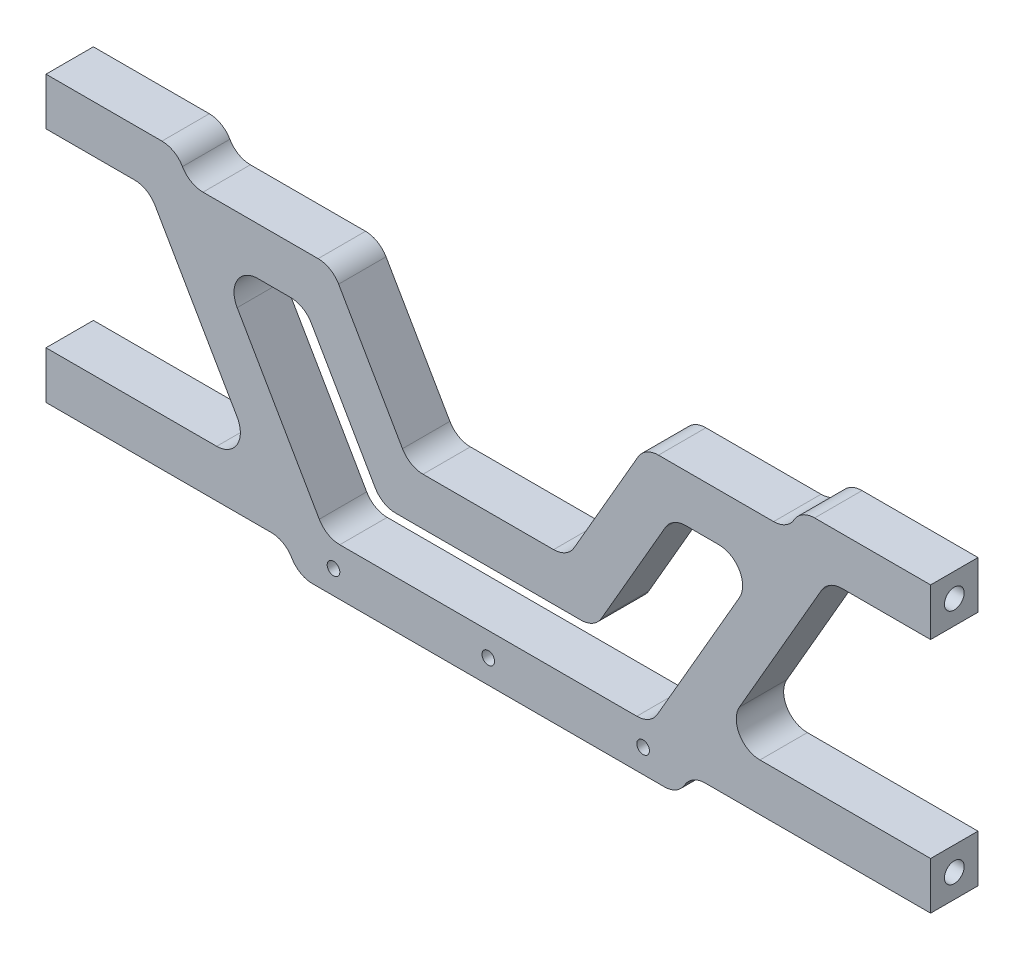
SolidWorks part; units mm, degrees
ref_plane "Front Plane" through (0, 0, 0) normal (0, 0, 1) x (1, 0, 0)
ref_plane "Top Plane" through (0, 0, 0) normal (0, 1, 0) x (1, 0, 0)
ref_plane "Right Plane" through (0, 0, 0) normal (1, 0, 0) x (0, 0, -1)
sketch "Sketch1" plane through (0, 0, 0) normal (0, 0, 1) x (1, 0, 0)
  line L1 (-56, 0) -> (56, 0)
  line L2 (-56, 0) -> (-56, 39)
  line L3 (-56, 39) -> (56, 39)
  line L4 (56, 0) -> (56, 39)
  dimension "D1" = 39
  dimension "D2" = 112
extrude "Boss-Extrude1" add sketch "Sketch1" along normal blind 6
sketch "Sketch2" plane through (0, 0, 6) normal (0, 0, 1) x (1, 0, 0)
  line L0 (-56, 33) -> (-43.0526, 33)
  line L2 (-56, 39) -> (-56, 0) construction
  line L3 (-43.0526, 33) -> (-29.1962, 9)
  line L5 (-29.1962, 9) -> (-56, 9)
  line L6 (-56, 9) -> (-56, 33)
  line L7 (56, 39) -> (-56, 39) construction
  line L8 (-39.5885, 39) -> (-37.8564, 36)
  line L9 (-10, 19) -> (0, 19)
  line L10 (0, 19) -> (0, 39)
  line L11 (0, 39) -> (-39.5885, 39)
  line L12 (-56, 3) -> (-25.7321, 3)
  line L13 (-25.7321, 3) -> (-24, 0)
  line L14 (-56, 0) -> (56, 0) construction
  line L15 (-24, 0) -> (-56, 0)
  line L16 (-56, 0) -> (-56, 3)
  line L17 (-13.4641, 13) -> (0, 13)
  line L18 (0, 13) -> (0, 6)
  line L19 (0, 6) -> (-20.5359, 6)
  line L20 (-20.5359, 6) -> (-34.3923, 30)
  line L21 (-37.8564, 36) -> (-19.815, 36)
  line L22 (-19.815, 36) -> (-10, 19)
  line L23 (-13.4641, 13) -> (-23.2791, 30)
  line L24 (-23.2791, 30) -> (-34.3923, 30)
  dimension "D3" = 60
  dimension "D1" = 6
  dimension "D2" = 24
  dimension "D4" = 6
  dimension "D5" = 3
  dimension "D6" = 24
  dimension "D7" = 6
  dimension "D8" = 6
  dimension "D9" = 3
  dimension "D10" = 6
  dimension "D11" = 6
  dimension "D12" = 20
  dimension "D13" = 10
extrude "Cut-Extrude1" cut sketch "Sketch2" against normal up to next
hole_wizard "Tap Drill for M3 Tap1" positions "Sketch4" profile "Sketch3" hole size "M3" standard "ISO"
sketch "Sketch4" plane through (-56, 0, 0) normal (-1, 0, 0) x (0, 0, 1)
  line L0 (6, 39) -> (0, 39) construction
  line L4 (0, 9) -> (0, 3) construction
  point P0 (3, 36)
  point P2 (3, 6)
  dimension "D1" = 3
  dimension "D2" = 30
  dimension "D3" = 3
sketch "Sketch3" plane through (-56, 36, 3) normal (0, 1, 0) x (0, 0, 1)
  line L0 (0, 0) -> (0, 10.7511)
  line L1 (0, 10.7511) -> (1.25, 10)
  line L2 (1.25, 10) -> (1.25, 0)
  line L5 (1.25, 0) -> (0, 0)
  line L10 (0, 10.7511) -> (-1.25, 10) construction
  line L11 (0, -6.35) -> (0, 107.95) construction
  dimension "Hole Dia." = 2.5
  dimension "Hole Depth" = 10
  dimension "Drill Angle" = 118
fillet "Fillet1" radius 3 12 edges at (-43.0526, 33, 3) (-29.1962, 9, 3) (-24, 0, 3) (-25.7321, 3, 3) (-39.5885, 39, 3) (-20.5359, 6, 3) (-37.8564, 36, 3) (-23.2791, 30, 3) (-19.815, 36, 3) (-34.3923, 30, 3) (-10, 19, 3) (-13.4641, 13, 3)
mirror "Mirror1" about plane through (0, 0, 0) normal (1, 0, 0) of "Fillet1", "Tap Drill for M3 Tap1", "Cut-Extrude1"
hole_wizard "Tap Drill for M2 Tap1" positions "Sketch7" profile "Sketch6" hole size "M2" standard "ISO" end condition up to next
sketch "Sketch7" plane through (0, 0, 6) normal (0, 0, 1) x (1, 0, 0)
  line L0 (-22.2679, 0) -> (22.2679, 0) construction
  point P0 (-19.6, 3)
  point P2 (0, 3)
  point P4 (19.6, 3)
  dimension "D1" = 19.6
  dimension "D2" = 19.6
  dimension "D3" = 3
sketch "Sketch6" plane through (-19.6, 3, 6) normal (1, 0, 0) x (0, -1, 0)
  line L0 (0, 0) -> (0, 6)
  line L1 (0, 6) -> (0.8, 6)
  line L2 (0.8, 6) -> (0.8, 0)
  line L5 (0.8, 0) -> (0, 0)
  line L11 (0, -6.35) -> (0, 107.95) construction
  dimension "Thru Hole Dia." = 1.6
  dimension "Thru Hole Depth" = 6
